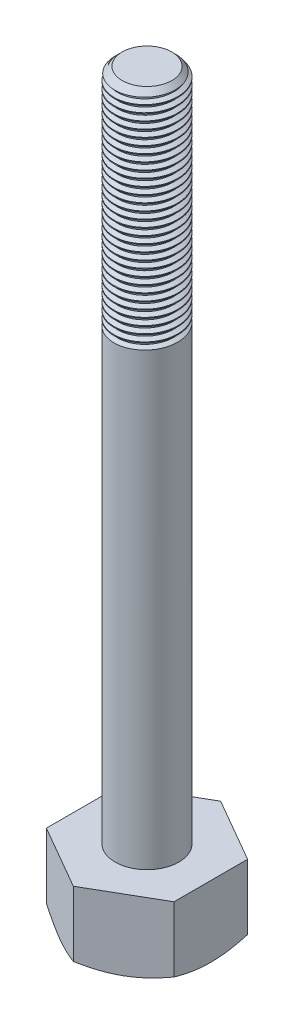
SolidWorks part; units mm, degrees
ref_plane "Front Plane" through (0, 0, 0) normal (0, 0, 1) x (1, 0, 0)
ref_plane "Top Plane" through (0, 0, 0) normal (0, 1, 0) x (1, 0, 0)
ref_plane "Right Plane" through (0, 0, 0) normal (1, 0, 0) x (0, 0, -1)
sketch "Sketch1" plane through (0, 0, 0) normal (0, 1, 0) x (1, 0, 0)
  line L1 (9, -5.1962) -> (9, 5.1962)
  line L2 (9, 5.1962) -> (0, 10.3923)
  line L3 (0, 10.3923) -> (-9, 5.1962)
  line L4 (-9, 5.1962) -> (-9, -5.1962)
  line L5 (-9, -5.1962) -> (0, -10.3923)
  line L6 (0, -10.3923) -> (9, -5.1962)
  circle A0 centre (0, 0) radius 4.5
  circle A1 centre (0, 0) radius 9 construction
  dimension "D2" = 9
  dimension "D1" = 18
extrude "Boss-Extrude1" add sketch "Sketch1" along normal blind 10
extrude "Boss-Extrude2" add sketch "Sketch1<2>" along normal blind 105 contours A0 region at (0, 0, 0)
sketch "Sketch1<2>" plane through (0, 0, 0) normal (0, 1, 0) x (1, 0, 0) same geometry as "Sketch1"
sketch "Sketch3" plane through (0, 0, 0) normal (0, 0, 1) x (1, 0, 0)
  line L0 (0, 0) -> (0, -50000) construction
  line L1 (9, 0) -> (15.465, 0)
  line L2 (15.465, 0) -> (15.465, 3.7326)
  line L3 (15.465, 3.7326) -> (9, 0)
  dimension "D1" = 30
revolve "Cut-Revolve1" cut sketch "Sketch3" angle 360 about L0
chamfer "Chamfer1" distance 1 angle 45 1 edges at (0, 105, 4.5)
thread "Thread1" pitch 1 method cut profile "Thread Profile1" start angle 0, offset 2, length 32, pitch 1, diameter 9
ref_plane "Plane1" through (-4.5, 106, 0) normal (0, 0, 1) x (-1, 0, 0)
sketch "Thread Profile1" plane through (-4.5, 106, 0) normal (0, 0, 1) x (-1, 0, 0)
  line L0 (0, 0) -> (0, 1) construction
  line L11 (0, 0) -> (0, 0.875)
  line L12 (0, 0.875) -> (-0.5413, 0.5625)
  line L13 (-0.5413, 0.5625) -> (-0.5413, 0.3125)
  line L15 (-0.5413, 0.3125) -> (0, 0)
  line L17 (-0.5413, 0.4375) -> (0, 0.4375) construction
  point P2 (0, 0)
  dimension "Pitch" = 1
  dimension "Profile_Angle" = 60
  dimension "Profile_Land" = 0.25
  dimension "Profile_Height" = 0.5413
